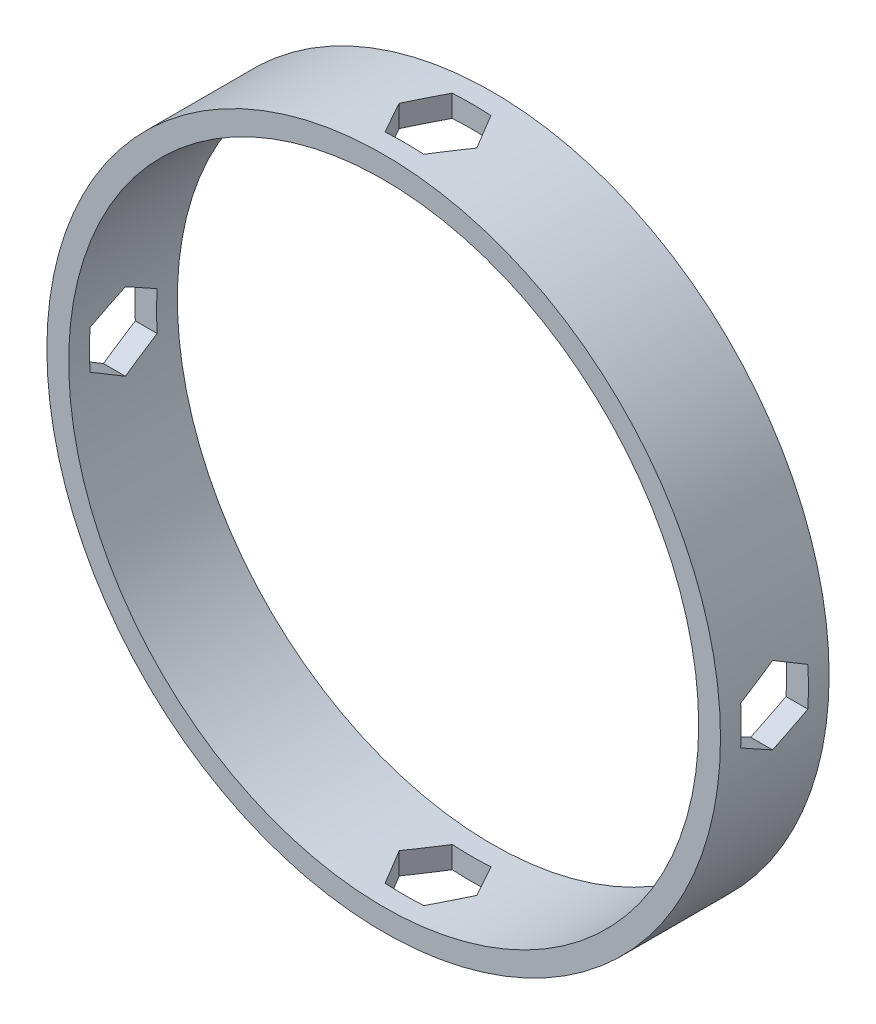
SolidWorks part; units mm, degrees
ref_plane "Front Plane" through (0, 0, 0) normal (0, 0, 1) x (1, 0, 0)
ref_plane "Top Plane" through (0, 0, 0) normal (0, 1, 0) x (1, 0, 0)
ref_plane "Right Plane" through (0, 0, 0) normal (1, 0, 0) x (0, 0, -1)
sketch "Sketch1" plane through (0, 0, 0) normal (0, 0, 1) x (1, 0, 0)
  circle A0 centre (0, 0) radius 34.11
  circle A1 centre (0, 0) radius 31.9
  dimension "D1" = 68.22
  dimension "D2" = 63.8
extrude "Boss-Extrude1" add sketch "Sketch1" along normal blind 10.5 and the other way blind 0.5
ref_plane "Plane1" through (0, 34.11, 0) normal (0, 1, 0) x (1, 0, 0)
sketch "Sketch2" plane through (0, 34.11, 0) normal (0, 1, 0) x (1, 0, 0)
  line L0 (0, -5) -> (-3.926, -5) construction
  line L1 (3.926, -5) -> (1.963, -1.6)
  line L2 (1.963, -1.6) -> (-1.963, -1.6)
  line L3 (-1.963, -1.6) -> (-3.926, -5)
  line L4 (-3.926, -5) -> (-1.963, -8.4)
  line L5 (-1.963, -8.4) -> (1.963, -8.4)
  line L6 (1.963, -8.4) -> (3.926, -5)
  circle A1 centre (0, -5) radius 3.4 construction
  dimension "D2" = 5
  dimension "D3" = 6.8
extrude "Cut-Extrude1" cut sketch "Sketch2" against normal through all
pattern_circular "CirPattern2" count 2 every 90 about axis through (0, 0, 10.5) along (0, 0, 1) of "Cut-Extrude1"
